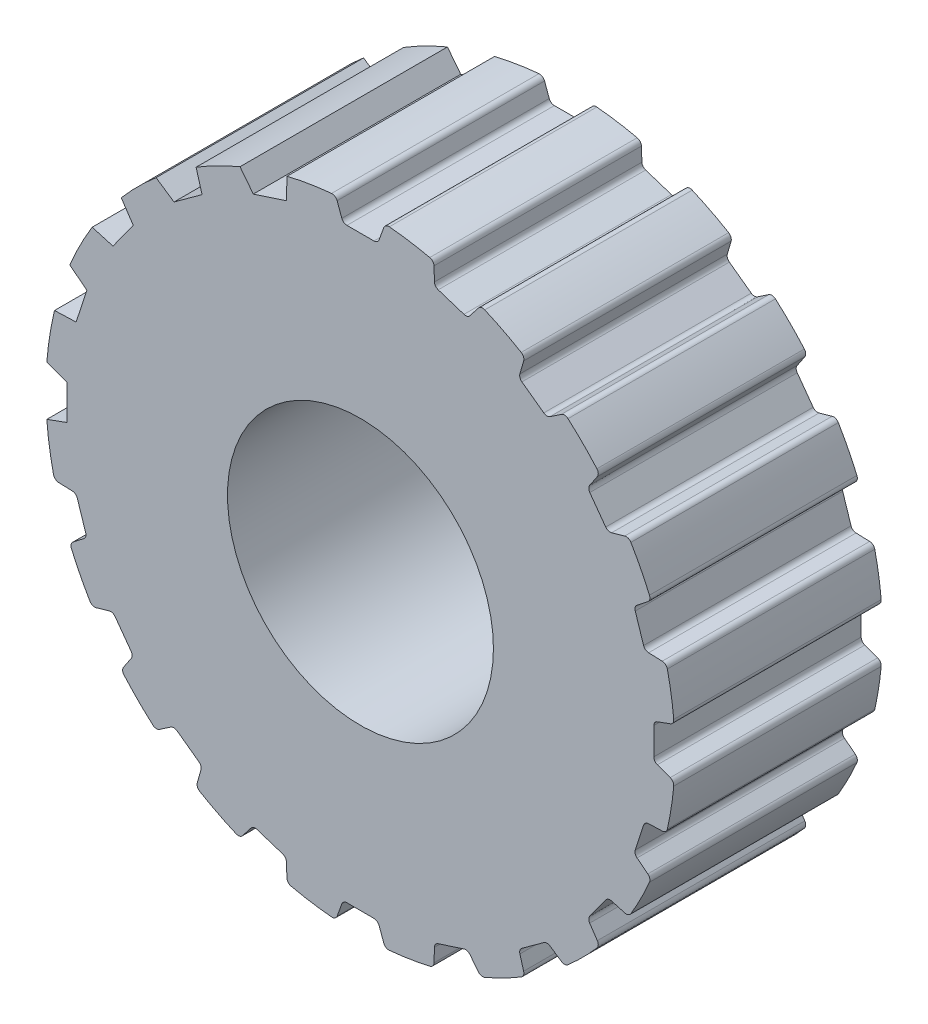
SolidWorks part; units mm, degrees
ref_plane "Front Plane" through (0, 0, 0) normal (0, 0, 1) x (1, 0, 0)
ref_plane "Top Plane" through (0, 0, 0) normal (0, 1, 0) x (1, 0, 0)
ref_plane "Right Plane" through (0, 0, 0) normal (1, 0, 0) x (0, 0, -1)
sketch "Sketch1" plane through (0, 0, 0) normal (0, 1, 0) x (1, 0, 0)
  line L0 (0, 36.1296) -> (0, -19.4741) construction
sketch "Sketch7" plane through (0, 0, 0) normal (0, 0, 1) x (1, 0, 0)
  line L0 (0, 0) -> (0, 28.5291) construction
  line L1 (-2.325, 29.4841) -> (-2.9401, 31.1741) construction
  line L2 (-2.325, 29.4841) -> (-1.6298, 27.5741) construction
  line L3 (-1.6298, 27.5741) -> (1.6298, 27.5741) construction
  line L4 (1.6298, 27.5741) -> (2.325, 29.4841) construction
  line L5 (2.325, 29.4841) -> (-2.325, 29.4841) construction
  line L6 (0, 27.5741) -> (0, 29.4841) construction
  line L7 (2.325, 29.4841) -> (2.9401, 31.1741) construction
  line L8 (-2.9401, 31.1741) -> (2.9401, 31.1741) construction
  line L9 (0, 0) -> (8.816, 27.1328) construction
  line L10 (8.816, 27.1328) -> (9.1394, 28.1281) construction
  line L11 (0, 29.4841) -> (0, 29.5757) construction
  line L12 (0, 29.5757) -> (0, 31.3125) construction
  line L13 (0, 30.4441) -> (9.4077, 28.954) construction
  line L14 (9.1394, 28.1281) -> (9.6761, 29.7799) construction
  circle A1 centre (0, 0) radius 28.5291 construction
  circle A2 centre (-1.2727, 28.0841) radius 0.51 construction
  circle A3 centre (1.2727, 28.0841) radius 0.51 construction
  circle A4 centre (0, 0) radius 29.5757
  circle A5 centre (0, 0) radius 31.3125 construction
  dimension "D3" = 40
  dimension "D6" = 1.02
  dimension "D1" = 3.6
  dimension "D2" = 18
  dimension "D7" = 9.525
  dimension "D4" = 1.91
  dimension "D5" = 4.65
extrude "Boss-Extrude1" add sketch "Sketch7" along normal blind 7.25 and the other way blind 7.25 contours A4 region at (0, 0, 0)
sketch "Sketch14" plane through (0, 0, 0) normal (1, 0, 0) x (0, 0, -1)
  line L0 (-21.5, 0) -> (-21.5, 10)
  line L1 (-21.5, 0) -> (0, 0)
  line L2 (0, 0) -> (0, 19)
  line L3 (0, 19) -> (-7.25, 19)
  line L4 (-7.25, 19) -> (-21.5, 10)
  line L5 (-7.25, 29.5757) -> (-7.25, -29.5757) construction
  line L6 (-21.5, 7.0431) -> (-2.5683, 19) construction
  arc A0 (-7.25, 19) -> (-21.5, 10) centre (-21.2919, 25.4517) cw
  dimension "D1" = 10
  dimension "D2" = 19
  dimension "D3" = 21.5
  dimension "D4" = 2.5
revolve "Revolve1" add sketch "Sketch14" angle 360 about L0 region at (0, 7.3866, 9.0486) region at (0, 9.3218, 19.3148) region at (0, 17.2024, 6.8722)
sketch "Sketch9" plane through (0, 0, 0) normal (0, 0, 1) x (1, 0, 0)
  line L0 (2, 0) -> (-2, 0) construction
  line L1 (-2, 0) -> (-2, 7.5) construction
  line L2 (-2, 7.5) -> (2, 7.5) construction
  line L3 (2, 7.5) -> (2, 0) construction
  circle A0 centre (0, 0) radius 6 construction
  dimension "D1" = 12
  dimension "D2" = 4
  dimension "D3" = 7.5
sketch "Sketch10" plane through (0, 0, 0) normal (0, 0, 1) x (1, 0, 0)
  line L0 (2, 0) -> (-2, 0) construction
  line L1 (-2.2, 7.7) -> (2.2, 7.7)
  line L2 (-2.2, 7.7) -> (-2.2, 0)
  line L3 (-2.2, 0) -> (2.2, 0)
  line L4 (2.2, 7.7) -> (2.2, 0)
  line L5 (-2, 7.5) -> (2, 7.5) construction
  line L6 (2, 7.5) -> (2, 0) construction
  circle A0 centre (0, 0) radius 6.2
  circle A1 centre (0, 0) radius 6 construction
  dimension "D1" = 0.2
  dimension "D2" = 0.2
  dimension "D3" = 0.2
extrude "Cut-Extrude3" cut sketch "Sketch10" against normal through all both and the other way through all contours A0 L4 L1 L2 | L2 A0 L4 L3 | L4 A0 L2 L3 region at (0, 6.8793, 0) region at (0, 3.0348, 0) region at (0, -0.8613, 0)
sketch "Sketch11" plane through (0, 0, 0) normal (0, 1, 0) x (1, 0, 0)
  line L0 (29.5757, 7.25) -> (-29.5757, 7.25) construction
  line L1 (11, 7.25) -> (17.5, 7.25)
  line L2 (11, 7.25) -> (11, 4.75)
  line L3 (11, 4.75) -> (17.5, 4.75)
  line L4 (17.5, 7.25) -> (17.5, 4.75)
  line L5 (-29.5757, -7.25) -> (29.5757, -7.25) construction
  line L6 (11, -7.25) -> (17.5, -7.25)
  line L7 (11, -7.25) -> (11, -4.75)
  line L8 (11, -4.75) -> (17.5, -4.75)
  line L9 (17.5, -7.25) -> (17.5, -4.75)
  line L11 (11, 4.75) -> (11, -4.75) construction
  line L12 (17.5, -4.75) -> (17.5, 4.75) construction
  line L13 (6.2, 7.25) -> (-6.2, 7.25) construction
  line L14 (0, 7.25) -> (22.5, 7.25)
  line L15 (0, 7.25) -> (0, -7.25)
  line L16 (0, -7.25) -> (22.5, -7.25)
  line L17 (22.5, 7.25) -> (22.5, -7.25)
  line L18 (-6.2, -7.25) -> (6.2, -7.25) construction
  line L19 (6, 7.25) -> (6, -7.25) construction
  dimension "D1" = 22.5
  dimension "D2" = 6
  dimension "D3" = 5
  dimension "D4" = 5
  dimension "D5" = 2.5
revolve "Cut-Revolve1" [suppressed] cut sketch "Sketch11" angle 360 about L0
sketch "Sketch15" plane through (0, 0, -7.25) normal (0, 0, -1) x (-1, 0, 0)
  circle A0 centre (0, 0) radius 8.0081
  circle A1 centre (0, 0) radius 2.25
  dimension "D1" = 4.5
extrude "Boss-Extrude2" add sketch "Sketch15" against normal blind 5.5
sketch "Sketch16" plane through (0, 0, -7.25) normal (0, 0, -1) x (-1, 0, 0)
  circle A0 centre (0, 0) radius 5
  dimension "D1" = 10
extrude "Cut-Extrude4" cut sketch "Sketch16" against normal blind 3
sketch "Sketch17" plane through (0, 0, -7.25) normal (0, 0, -1) x (-1, 0, 0)
  circle A0 centre (0, 0) radius 29.5757
  circle A1 centre (0, 0) radius 29.5757 construction
  circle A2 centre (0, 0) radius 5
  circle A3 centre (0, 0) radius 5 construction
extrude "Boss-Extrude3" add sketch "Sketch17" along normal blind 7.5
sketch "Sketch8" plane through (0, 0, 0) normal (0, 0, 1) x (1, 0, 0)
  line L6 (-1.6298, 27.5741) -> (-2.3583, 29.5757)
  line L7 (-2.3583, 29.5757) -> (2.3583, 29.5757)
  line L8 (2.3583, 29.5757) -> (1.6298, 27.5741)
  line L9 (1.6298, 27.5741) -> (-1.6298, 27.5741)
  line L10 (-2.325, 29.4841) -> (-1.6298, 27.5741) construction
  line L11 (1.6298, 27.5741) -> (2.325, 29.4841) construction
  line L12 (6.9708, 26.7282) -> (6.8965, 28.8569)
  line L13 (6.8965, 28.8569) -> (11.3823, 27.3994)
  line L14 (11.3823, 27.3994) -> (10.0709, 25.7209)
  line L15 (10.0709, 25.7209) -> (6.9708, 26.7282)
  line L16 (14.8891, 23.2659) -> (15.4762, 25.3134)
  line L17 (15.4762, 25.3134) -> (19.292, 22.541)
  line L18 (19.292, 22.541) -> (17.5262, 21.35)
  line L19 (17.5262, 21.35) -> (14.8891, 23.2659)
  line L20 (21.35, 17.5262) -> (22.541, 19.292)
  line L21 (22.541, 19.292) -> (25.3134, 15.4762)
  line L22 (25.3134, 15.4762) -> (23.2659, 14.8891)
  line L23 (23.2659, 14.8891) -> (21.35, 17.5262)
  line L24 (25.7209, 10.0709) -> (27.3994, 11.3823)
  line L25 (27.3994, 11.3823) -> (28.8569, 6.8965)
  line L26 (28.8569, 6.8965) -> (26.7282, 6.9708)
  line L27 (26.7282, 6.9708) -> (25.7209, 10.0709)
  line L28 (27.5741, 1.6298) -> (29.5757, 2.3583)
  line L29 (29.5757, 2.3583) -> (29.5757, -2.3583)
  line L30 (29.5757, -2.3583) -> (27.5741, -1.6298)
  line L31 (27.5741, -1.6298) -> (27.5741, 1.6298)
  line L32 (26.7282, -6.9708) -> (28.8569, -6.8965)
  line L33 (28.8569, -6.8965) -> (27.3994, -11.3823)
  line L34 (27.3994, -11.3823) -> (25.7209, -10.0709)
  line L35 (25.7209, -10.0709) -> (26.7282, -6.9708)
  line L36 (23.2659, -14.8891) -> (25.3134, -15.4762)
  line L37 (25.3134, -15.4762) -> (22.541, -19.292)
  line L38 (22.541, -19.292) -> (21.35, -17.5262)
  line L39 (21.35, -17.5262) -> (23.2659, -14.8891)
  line L40 (17.5262, -21.35) -> (19.292, -22.541)
  line L41 (19.292, -22.541) -> (15.4762, -25.3134)
  line L42 (15.4762, -25.3134) -> (14.8891, -23.2659)
  line L43 (14.8891, -23.2659) -> (17.5262, -21.35)
  line L44 (10.0709, -25.7209) -> (11.3823, -27.3994)
  line L45 (11.3823, -27.3994) -> (6.8965, -28.8569)
  line L46 (6.8965, -28.8569) -> (6.9708, -26.7282)
  line L47 (6.9708, -26.7282) -> (10.0709, -25.7209)
  line L48 (1.6298, -27.5741) -> (2.3583, -29.5757)
  line L49 (2.3583, -29.5757) -> (-2.3583, -29.5757)
  line L50 (-2.3583, -29.5757) -> (-1.6298, -27.5741)
  line L51 (-1.6298, -27.5741) -> (1.6298, -27.5741)
  line L52 (-6.9708, -26.7282) -> (-6.8965, -28.8569)
  line L53 (-6.8965, -28.8569) -> (-11.3823, -27.3994)
  line L54 (-11.3823, -27.3994) -> (-10.0709, -25.7209)
  line L55 (-10.0709, -25.7209) -> (-6.9708, -26.7282)
  line L56 (-14.8891, -23.2659) -> (-15.4762, -25.3134)
  line L57 (-15.4762, -25.3134) -> (-19.292, -22.541)
  line L58 (-19.292, -22.541) -> (-17.5262, -21.35)
  line L59 (-17.5262, -21.35) -> (-14.8891, -23.2659)
  line L60 (-21.35, -17.5262) -> (-22.541, -19.292)
  line L61 (-22.541, -19.292) -> (-25.3134, -15.4762)
  line L62 (-25.3134, -15.4762) -> (-23.2659, -14.8891)
  line L63 (-23.2659, -14.8891) -> (-21.35, -17.5262)
  line L64 (-25.7209, -10.0709) -> (-27.3994, -11.3823)
  line L65 (-27.3994, -11.3823) -> (-28.8569, -6.8965)
  line L66 (-28.8569, -6.8965) -> (-26.7282, -6.9708)
  line L67 (-26.7282, -6.9708) -> (-25.7209, -10.0709)
  line L68 (-27.5741, -1.6298) -> (-29.5757, -2.3583)
  line L69 (-29.5757, -2.3583) -> (-29.5757, 2.3583)
  line L70 (-29.5757, 2.3583) -> (-27.5741, 1.6298)
  line L71 (-27.5741, 1.6298) -> (-27.5741, -1.6298)
  line L72 (-26.7282, 6.9708) -> (-28.8569, 6.8965)
  line L73 (-28.8569, 6.8965) -> (-27.3994, 11.3823)
  line L74 (-27.3994, 11.3823) -> (-25.7209, 10.0709)
  line L75 (-25.7209, 10.0709) -> (-26.7282, 6.9708)
  line L76 (-23.2659, 14.8891) -> (-25.3134, 15.4762)
  line L77 (-25.3134, 15.4762) -> (-22.541, 19.292)
  line L78 (-22.541, 19.292) -> (-21.35, 17.5262)
  line L79 (-21.35, 17.5262) -> (-23.2659, 14.8891)
  line L80 (-17.5262, 21.35) -> (-19.292, 22.541)
  line L81 (-19.292, 22.541) -> (-15.4762, 25.3134)
  line L82 (-15.4762, 25.3134) -> (-14.8891, 23.2659)
  line L83 (-14.8891, 23.2659) -> (-17.5262, 21.35)
  line L84 (-10.0709, 25.7209) -> (-11.3823, 27.3994)
  line L85 (-11.3823, 27.3994) -> (-6.8965, 28.8569)
  line L86 (-6.8965, 28.8569) -> (-6.9708, 26.7282)
  line L87 (-6.9708, 26.7282) -> (-10.0709, 25.7209)
  circle A0 centre (0, 0) radius 29.5757 construction
  point P119 (0, 0)
  dimension "D1" = 20
extrude "Cut-Extrude2" cut sketch "Sketch8" against normal through all both and the other way through all
fillet "Fillet2" radius 0.51 60 edges at (-28.7595, -6.8999, -3.75) (-27.3226, -11.3223, -3.75) (-25.2198, -15.4494, -3.75) (-22.4866, -19.2113, -3.75) (-19.2113, -22.4866, -3.75) (-15.4494, -25.2198, -3.75) (-11.3223, -27.3226, -3.75) (-6.8999, -28.7595, -3.75) (-2.325, -29.4841, -3.75) (2.325, -29.4841, -3.75) (6.8999, -28.7595, -3.75) (11.3223, -27.3226, -3.75) (15.4494, -25.2198, -3.75) (19.2113, -22.4866, -3.75) (22.4866, -19.2113, -3.75) (25.2198, -15.4494, -3.75) (27.3226, -11.3223, -3.75) (28.7595, -6.8999, -3.75) (29.4841, -2.325, -3.75) (29.4841, 2.325, -3.75) (28.7595, 6.8999, -3.75) (27.3226, 11.3223, -3.75) (25.2198, 15.4494, -3.75) (22.4866, 19.2113, -3.75) (19.2113, 22.4866, -3.75) (15.4494, 25.2198, -3.75) (11.3223, 27.3226, -3.75) (6.8999, 28.7595, -3.75) (2.325, 29.4841, -3.75) (-26.7282, -6.9708, -3.75) (-25.7209, -10.0709, -3.75) (-23.2659, -14.8891, -3.75) (-21.35, -17.5262, -3.75) (-17.5262, -21.35, -3.75) (-14.8891, -23.2659, -3.75) (-10.0709, -25.7209, -3.75) (-6.9708, -26.7282, -3.75) (-1.6298, -27.5741, -3.75) (1.6298, -27.5741, -3.75) (6.9708, -26.7282, -3.75) (10.0709, -25.7209, -3.75) (14.8891, -23.2659, -3.75) (17.5262, -21.35, -3.75) (21.35, -17.5262, -3.75) (23.2659, -14.8891, -3.75) (25.7209, -10.0709, -3.75) (26.7282, -6.9708, -3.75) (27.5741, -1.6298, -3.75) (27.5741, 1.6298, -3.75) (26.7282, 6.9708, -3.75) (25.7209, 10.0709, -3.75) (23.2659, 14.8891, -3.75) (21.35, 17.5262, -3.75) (17.5262, 21.35, -3.75) (14.8891, 23.2659, -3.75) (10.0709, 25.7209, -3.75) (6.9708, 26.7282, -3.75) (1.6298, 27.5741, -3.75) (-1.6298, 27.5741, -3.75) (-2.325, 29.4841, -3.75)
sketch "Sketch18" plane through (0, 0, -14.75) normal (0, 0, -1) x (-1, 0, 0)
  circle A0 centre (0, 0) radius 5
  circle A1 centre (0, 0) radius 34.5757
  circle A2 centre (0, 0) radius 29.5757
  circle A3 centre (0, 0) radius 5 construction
  arc A4 (-2.7175, 29.4505) -> (-6.5162, 28.8489) centre (0, 0) ccw construction
  dimension "D1" = 5
extrude "Boss-Extrude4" add sketch "Sketch18" along normal blind 2.5 contours A1 A2 | A2 A0 region at (33.5977, 0, -14.75) region at (28.7391, 0, -14.75)
sketch "Sketch19" plane through (0, 0, 7.25) normal (0, 0, 1) x (1, 0, 0)
  circle A0 centre (0, 0) radius 19
  circle A1 centre (0, 0) radius 34.5757
  circle A2 centre (0, 0) radius 34.5757 construction
  circle A3 centre (0, 0) radius 19 construction
extrude "Boss-Extrude5" add sketch "Sketch19" against normal blind 2.5
fillet "Fillet3" radius 0.5 19 edges at (2.2, 5.7966, 9.875) (-2.2, 5.7966, 9.875) (2.2, 6.7483, 21.5) (-2.2, 6.7483, 21.5) (0, 7.7, 21.5) (-19, 0, 7.25) (-10, 0, 21.5) (0, -6.2, 21.5) (-5, 0, -4.25) (-2.25, 0, -4.25) (-2.2, 6.7483, -1.75) (2.2, 6.7483, -1.75) (34.5757, 0, 4.75) (-34.5757, 0, -14.75) (-34.5757, 0, -17.25) (34.5757, 0, 7.25) (0, 7.7, -1.75) (0, -6.2, -1.75) (-5, 0, -17.25)
sketch "Sketch20" plane through (0, 0, 0) normal (1, 0, 0) x (0, 0, -1)
  line L0 (-4.75, -34.0757) -> (-4.75, 34.0757) construction
  line L1 (-21.5, 34.5757) -> (17.25, 34.5757)
  line L2 (-21.5, 34.5757) -> (-21.5, -34.5757)
  line L3 (-21.5, -34.5757) -> (17.25, -34.5757)
  line L4 (17.25, 34.5757) -> (17.25, -34.5757)
  line L5 (14.75, -34.5757) -> (-4.75, -34.5757)
  line L6 (14.75, -34.5757) -> (14.75, 34.5757)
  line L7 (14.75, 34.5757) -> (-4.75, 34.5757)
  line L8 (-4.75, -34.5757) -> (-4.75, 34.5757)
  line L9 (14.75, 34.0757) -> (14.75, -34.0757) construction
  line L10 (15.25, -34.5757) -> (16.75, -34.5757) construction
  line L11 (-21.5, 9.5013) -> (-21.5, -9.5013) construction
  line L12 (17.25, -34.0757) -> (17.25, 34.0757) construction
extrude "Cut-Extrude5" cut sketch "Sketch20" against normal through all both and the other way through all contours L3 L8 L1 L2 | L6 L3 L4 L1 region at (0, 0, 13.125) region at (0, 0, -16)
sketch "Sketch21" plane through (0, 0, 0) normal (0, 0, 1) x (1, 0, 0)
  circle A0 centre (0, 0) radius 12.5
  dimension "D1" = 25
extrude "Cut-Extrude6" cut sketch "Sketch21" against normal through all both and the other way through all
